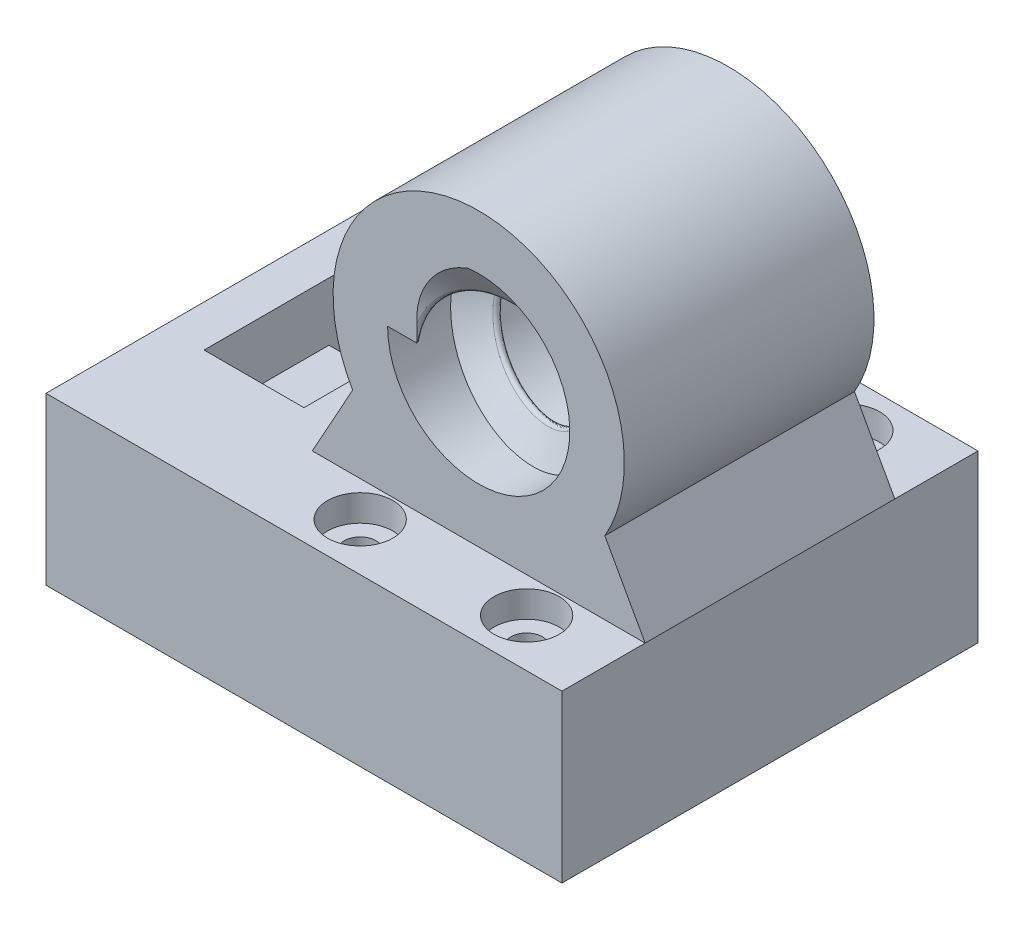
SolidWorks part; units mm, degrees
ref_plane "Front Plane" through (0, 0, 0) normal (0, 0, 1) x (1, 0, 0)
ref_plane "Top Plane" through (0, 0, 0) normal (0, 1, 0) x (1, 0, 0)
ref_plane "Right Plane" through (0, 0, 0) normal (1, 0, 0) x (0, 0, -1)
sketch "Sketch1" plane through (0, 0, 0) normal (0, 0, 1) x (1, 0, 0)
  circle A0 centre (0, 0) radius 17.5
  dimension "D1" = 35
extrude "Boss-Extrude1" add sketch "Sketch1" along normal blind 30
sketch "Sketch5" plane through (0, 0, 0) normal (0, 0, -1) x (-1, 0, 0)
  circle A0 centre (0, 0) radius 10.95
  dimension "D1" = 21.9
extrude "Cut-Extrude2" cut sketch "Sketch5" against normal through all
ref_plane "Plane1" through (0, 0, -10) normal (0, 0, -1) x (-1, 0, 0)
sketch "Sketch6" plane through (0, 0, -10) normal (0, 0, -1) x (-1, 0, 0)
  circle A0 centre (0, 0) radius 10.95 construction
  circle A1 centre (0, 0) radius 10.95
curve "Helix/Spiral2" pitch 10 height 40 turns 4
sketch "Sketch7" plane through (0, 0, 0) normal (1, 0, 0) x (0, 0, -1)
  line L0 (7.5, -6.95) -> (7.5, -10.95) construction
  line L1 (7.067, -7.7) -> (5.1906, -10.95)
  line L2 (5.1906, -10.95) -> (9.8094, -10.95)
  line L3 (7.933, -7.7) -> (9.8094, -10.95)
  arc A0 (7.933, -7.7) -> (7.067, -7.7) centre (7.5, -7.95) ccw
  point P8 (0, 0)
  dimension "D3" = 0.5
  dimension "D1" = 60
  dimension "D2" = 4
sweep "Sweep2" add profiles "Sketch7" path "Helix/Spiral2"
sketch "Sketch8" plane through (0, 0, 0) normal (0, 0, -1) x (-1, 0, 0)
  circle A0 centre (0, 0) radius 17.5
  circle A1 centre (0, 0) radius 17.5 construction
extrude "Cut-Extrude3" cut sketch "Sketch8" along normal through all
sketch "Sketch9" plane through (0, 0, 30) normal (0, 0, 1) x (1, 0, 0)
  circle A0 centre (0, 0) radius 17.5
  circle A1 centre (0, 0) radius 17.5 construction
extrude "Cut-Extrude4" cut sketch "Sketch9" along normal through all
sketch "Sketch10" plane through (0, 0, 0) normal (0, 0, -1) x (-1, 0, 0)
  line L0 (-20, -17.5) -> (0, 0) construction
  line L1 (-20, -17.5) -> (20, -17.5)
  line L2 (-20, -17.5) -> (-20, -37.4773)
  line L3 (-20, -37.4773) -> (20, -37.4773)
  line L4 (20, -17.5) -> (20, -37.4773)
  line L5 (0, 0) -> (20, -17.5) construction
  circle A0 centre (0, 0) radius 17.5 construction
  dimension "D1" = 40
  dimension "D2" = 19.9773
extrude "Boss-Extrude2" add sketch "Sketch10" against normal blind 40 separate body
sketch "Sketch11" plane through (0, 0, 0) normal (0, 0, -1) x (-1, 0, 0)
  line L1 (-20, -17.5) -> (20, -17.5)
  line L2 (-20, -17.5) -> (-20, -37.4773)
  line L3 (-20, -37.4773) -> (20, -37.4773)
  line L4 (20, -17.5) -> (20, -37.4773)
extrude "Boss-Extrude3" add sketch "Sketch11" along normal blind 10
sketch "Sketch13" plane through (0, 0, 0) normal (0, 0, -1) x (-1, 0, 0)
  line L0 (0, -17.5) -> (-20, -17.5)
  line L1 (20, -17.5) -> (-20, -17.5) construction
  line L2 (-20, -17.5) -> (-15.1539, -8.7527)
  circle A0 centre (0, 0) radius 17.5 construction
  arc A1 (-15.1539, -8.7527) -> (0, -17.5) centre (0, 0) ccw
  dimension "D1" = 10
extrude "Boss-Extrude4" add sketch "Sketch13" against normal up to surface (30 mm away) up to face at (-3.7285, 0.054, 30)
ref_plane "Plane2" through (0, 0, 0) normal (1, 0, 0) x (0, 0, -1)
mirror "Mirror1" about plane through (0, 0, 0) normal (1, 0, 0) of "Boss-Extrude4"
sketch "Sketch14" plane through (0, -37.4773, 0) normal (0, -1, 0) x (1, 0, 0)
  line L0 (-20, 40) -> (20, -10) construction
  line L2 (-20, -10) -> (20, 40) construction
  line L3 (10, -4.2426) -> (-10, -4.2426) construction
  line L4 (10, -4.2426) -> (10, 34.2426) construction
  line L5 (10, 34.2426) -> (-10, 34.2426) construction
  line L6 (-10, -4.2426) -> (-10, 34.2426) construction
  line L7 (10, -4.2426) -> (-10, 34.2426) construction
  line L8 (10, 34.2426) -> (-10, -4.2426) construction
  circle A0 centre (-10, 34.2426) radius 1.905
  circle A1 centre (10, 34.2426) radius 1.905
  circle A2 centre (-10, -4.2426) radius 1.905
  circle A3 centre (10, -4.2426) radius 1.905
  point P8 (0, 15)
  dimension "D3" = 3.81
  dimension "D1" = 38.4853
  dimension "D2" = 20
extrude "Cut-Extrude5" cut sketch "Sketch14" against normal through all
ref_plane "Plane3" through (0, -20.6734, 0) normal (0, 1, 0) x (1, 0, 0)
sketch "Sketch15" plane through (0, -20.6734, 0) normal (0, 1, 0) x (1, 0, 0)
  circle A0 centre (-10, 4.2426) radius 3.9243
  circle A1 centre (10, 4.2426) radius 3.9243
  circle A2 centre (10, -34.2426) radius 3.9243
  circle A3 centre (-10, -34.2426) radius 3.9243
  dimension "D1" = 7.8486
extrude "Cut-Extrude7" cut sketch "Sketch15" along normal through all
sketch "Sketch16" plane through (-20, 0, 0) normal (-1, 0, 0) x (0, 0, 1)
  line L0 (40, -37.4773) -> (40, -17.5) construction
  line L1 (-10, -17.5) -> (40, -17.5)
  line L2 (-10, -17.5) -> (-10, -37.4773)
  line L3 (-10, -37.4773) -> (40, -37.4773)
  line L4 (40, -17.5) -> (40, -37.4773)
  line L5 (40, -37.4773) -> (-10, -37.4773) construction
extrude "Boss-Extrude5" add sketch "Sketch16" along normal blind 22
ref_plane "Plane4" through (-37, 0, 0) normal (-1, 0, 0) x (0, 0, 1)
sketch "Sketch17" plane through (-37, 0, 0) normal (-1, 0, 0) x (0, 0, 1)
  line L0 (40, -17.5) -> (-10, -17.5) construction
  line L5 (4, -24.5) -> (-10, -17.5) construction
  line L6 (40, -17.5) -> (26, -24.5) construction
  line L12 (4, -24.5) -> (8.5, -24.5)
  line L13 (11, -24.5) -> (26, -24.5)
  line L14 (26, -17.5) -> (4, -17.5)
  line L15 (4, -17.5) -> (4, -24.5)
  line L16 (26, -17.5) -> (26, -24.5)
  line L17 (8.5, -24.5) -> (8.5, -29.4889)
  line L18 (11, -24.5) -> (11, -29.4889)
  line L19 (8.5, -29.4889) -> (11, -29.4889)
  dimension "D1" = 22
  dimension "D2" = 7
  dimension "D3" = 2.5
  dimension "D4" = 4.5
extrude "Cut-Extrude8" cut sketch "Sketch17" against normal blind 12
